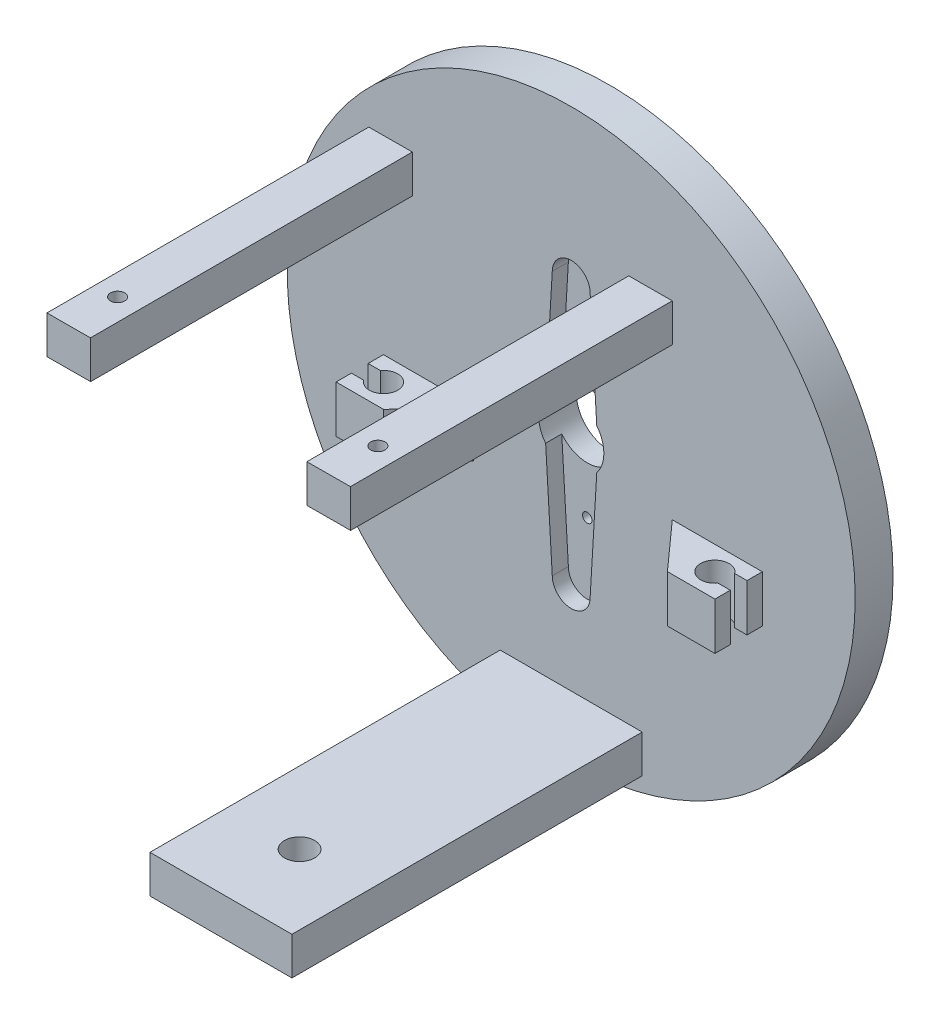
SolidWorks part; units mm, degrees
ref_plane "Front Plane" through (0, 0, 0) normal (0, 0, 1) x (1, 0, 0)
ref_plane "Top Plane" through (0, 0, 0) normal (0, 1, 0) x (1, 0, 0)
ref_plane "Right Plane" through (0, 0, 0) normal (1, 0, 0) x (0, 0, -1)
sketch "Sketch1" plane through (0, 0, 0) normal (0, 0, 1) x (1, 0, 0)
  circle A0 centre (-30, 0) radius 30
  dimension "D1" = 60
extrude "Boss-Extrude1" add sketch "Sketch1" against normal blind 4
sketch "Sketch2" plane through (0, 0, 0) normal (0, 0, 1) x (1, 0, 0)
  line L4 (-32, 13.925) -> (-32.7, 2.1477)
  line L5 (-27.3, 2.1477) -> (-28, 13.925)
  line L6 (-28, -13.925) -> (-27.3, -2.1477)
  line L7 (-32.7, -2.1477) -> (-32, -13.925)
  arc A3 (-32, -13.925) -> (-28, -13.925) centre (-30, -13.925) ccw
  arc A6 (-32.7, 2.1477) -> (-32.7, -2.1477) centre (-30, 0) ccw
  arc A7 (-27.3, -2.1477) -> (-27.3, 2.1477) centre (-30, 0) ccw
  arc A8 (-28, 13.925) -> (-32, 13.925) centre (-30, 13.925) ccw
  dimension "D1" = 2
  dimension "D2" = 2
extrude "Cut-Extrude1" cut sketch "Sketch2" against normal through all
sketch "Sketch3" plane through (0, 0, -4) normal (0, 0, -1) x (-1, 0, 0)
  line L0 (27.3, -2.1477) -> (28, -13.925)
  line L1 (32, -13.925) -> (32.7, -2.1477)
  line L2 (32, 13.925) -> (32.7, 2.1477)
  line L3 (28, 13.925) -> (27.3, 2.1477)
  arc A0 (27.3, -2.1477) -> (32.7, -2.1477) centre (30, 0) ccw
  arc A1 (32, 13.925) -> (28, 13.925) centre (30, 13.925) ccw
  arc A2 (28, -13.925) -> (32, -13.925) centre (30, -13.925) ccw
  arc A3 (32.7, 2.1477) -> (27.3, 2.1477) centre (30, 0) ccw
extrude "Boss-Extrude2" add sketch "Sketch3" against normal blind 2.3
sketch "Sketch4" plane through (0, 0, 0) normal (0, 0, 1) x (1, 0, 0)
  line L0 (-23.9048, 13.5471) -> (-19.3048, 13.567)
  line L13 (-23.9048, 13.5471) -> (-23.9221, 17.5471)
  line L15 (-19.3048, 13.567) -> (-19.3221, 17.5669)
  line L16 (-23.9221, 17.5471) -> (-19.3221, 17.5669)
  line L17 (-51.3645, 13.4286) -> (-46.7646, 13.4485)
  line L18 (-51.3645, 13.4286) -> (-51.3818, 17.4286)
  line L19 (-46.7646, 13.4485) -> (-46.7819, 17.4484)
  line L20 (-51.3818, 17.4286) -> (-46.7819, 17.4484)
  line L21 (-30, 30) -> (-50030, 30) construction
  dimension "D1" = 4
  dimension "D2" = 4
extrude "Boss-Extrude3" add sketch "Sketch4" along normal blind 34
sketch "Sketch5" plane through (-0.0589, 13.65, 0) normal (0.0043, -1, 0) x (1, 0.0043, 0)
  circle A0 centre (-49.0261, 28.8183) radius 0.75
  circle A1 centre (-21.5261, 28.8183) radius 0.75
  dimension "D1" = 1.5
  dimension "D2" = 1.5
extrude "Cut-Extrude2" cut sketch "Sketch5" against normal through all
sketch "Sketch6" plane through (0, 0, 0) normal (0, 0, 1) x (1, 0, 0)
  circle A0 centre (-30.004, -8.465) radius 0.5
  circle A1 centre (-29.996, 8.465) radius 0.5
  dimension "D1" = 1
  dimension "D2" = 1
extrude "Cut-Extrude3" cut sketch "Sketch6" against normal blind 10
sketch "Sketch7" plane through (0, 0, 0) normal (0, 0, 1) x (1, 0, 0)
  line L0 (-30, -30) -> (-30, 30) construction
  line L2 (-22.5, -27.4741) -> (-37.5, -27.4741)
  line L3 (-22.5, -27.4741) -> (-22.5, -23.4741)
  line L4 (-22.5, -23.4741) -> (-37.5, -23.4741)
  line L5 (-37.5, -27.4741) -> (-37.5, -23.4741)
  line L6 (-22.5, -27.4741) -> (-37.5, -23.4741) construction
  line L7 (-22.5, -23.4741) -> (-37.5, -27.4741) construction
  circle A0 centre (-30, 0) radius 30 construction
  point P5 (-30, -25.4741)
  dimension "D1" = 15
  dimension "D2" = 4
extrude "Boss-Extrude4" add sketch "Sketch7" along normal blind 37
sketch "Sketch8" plane through (0, -27.4741, 0) normal (0, -1, 0) x (1, 0, 0)
  circle A0 centre (-29.8789, 28.8183) radius 1.6
  dimension "D1" = 3.2
extrude "Cut-Extrude4" cut sketch "Sketch8" against normal blind 37
sketch "Sketch9" plane through (0, 0, 0) normal (0, 0, 1) x (1, 0, 0)
  line L1 (-9.8141, -7.4423) -> (-14.8356, -7.4423)
  line L2 (-9.8141, -7.4423) -> (-9.8141, -2.4639)
  line L3 (-9.8141, -2.4639) -> (-14.8356, -2.4639)
  line L4 (-14.8356, -7.4423) -> (-14.8356, -2.4639)
  line L5 (-12.3249, -2.4639) -> (-12.3249, -7.4423) construction
  line L6 (-9.8141, -4.9531) -> (-14.8356, -4.9531) construction
  line L7 (-44.8138, -7.5933) -> (-49.8353, -7.5933)
  line L8 (-44.8138, -7.5933) -> (-44.8138, -2.6149)
  line L9 (-44.8138, -2.6149) -> (-49.8353, -2.6149)
  line L10 (-49.8353, -7.5933) -> (-49.8353, -2.6149)
  line L11 (-47.3245, -2.6149) -> (-47.3245, -7.5933) construction
  line L12 (-44.8138, -5.1041) -> (-49.8353, -5.1041) construction
  point P148 (-47.3245, -5.1041)
  point P192 (-12.3249, -4.9531)
extrude "Boss-Extrude5" add sketch "Sketch9" along normal blind 5
sketch "Sketch11" plane through (0, -7.4423, 0) normal (0, -1, 0) x (1, 0, 0)
  line L0 (-12.3249, 5) -> (-12.3249, 0) construction
  line L1 (-14.8356, 5) -> (-9.8141, 5) construction
  line L2 (-14.8356, 0) -> (-9.8141, 0) construction
  line L3 (-14.8356, 2.5) -> (-9.8141, 2.5) construction
  line L4 (-14.8356, 5) -> (-14.8356, 0) construction
  line L5 (-9.8141, 5) -> (-9.8141, 0) construction
  line L6 (-29.8247, 2.5) -> (-29.8247, 50002.5) construction
  line L7 (-9.8141, 1.6163) -> (-11.1128, 1.6163)
  line L8 (-9.8141, 1.6163) -> (-9.8141, 3.3837)
  line L9 (-9.8141, 3.3837) -> (-11.1128, 3.3837)
  line L11 (-10.4635, 3.3837) -> (-10.4635, 1.6163) construction
  line L12 (-9.8141, 2.5) -> (-11.1128, 2.5) construction
  line L13 (0, 0) -> (-60, 0) construction
  line L17 (-49.8353, 2.5) -> (-9.8141, 2.5) construction
  line L18 (-49.8353, 5) -> (-49.8353, 0) construction
  line L19 (-49.8353, 3.3837) -> (-48.5366, 3.3837)
  line L20 (-49.8353, 1.6163) -> (-49.8353, 3.3837)
  line L21 (-49.8353, 1.6163) -> (-48.5366, 1.6163)
  arc A0 (-11.1128, 3.3837) -> (-11.1128, 1.6163) centre (-12.3249, 2.5) ccw
  arc A2 (-48.5366, 3.3837) -> (-48.5366, 1.6163) centre (-47.3245, 2.5) cw
  point P23 (-29.8247, 2.5)
  point P326 (-10.4635, 2.5)
  dimension "D1" = 3
extrude "Cut-Extrude5" cut sketch "Sketch11" against normal blind 15 and the other way blind 5
sketch "Sketch12" plane through (0, -2.4639, 0) normal (0, 1, 0) x (1, 0, 0)
  line L0 (-14.8356, -5) -> (-19.3221, 0)
  line L1 (-19.3221, 0) -> (-14.8356, 0)
  line L2 (-14.8356, 0) -> (-14.8356, -5)
  dimension "D1" = 4.4865
extrude "Boss-Extrude6" add sketch "Sketch12" against normal up to surface (4.9784 mm away) up to face at (-11.7332, -7.4423, 2.5)
sketch "Sketch13" plane through (0, -2.6149, 0) normal (0, 1, 0) x (1, 0, 0)
  line L0 (-44.8138, -5) -> (-44.8138, 0)
  line L1 (-44.8138, 0) -> (-40.3138, 0)
  line L2 (-60, 0) -> (0, 0) construction
  line L3 (-40.3138, 0) -> (-44.8138, -5)
  dimension "D1" = 4.5
extrude "Boss-Extrude7" add sketch "Sketch13" against normal up to surface (4.9784 mm away) up to face at (-47.9162, -7.5933, 2.5)
